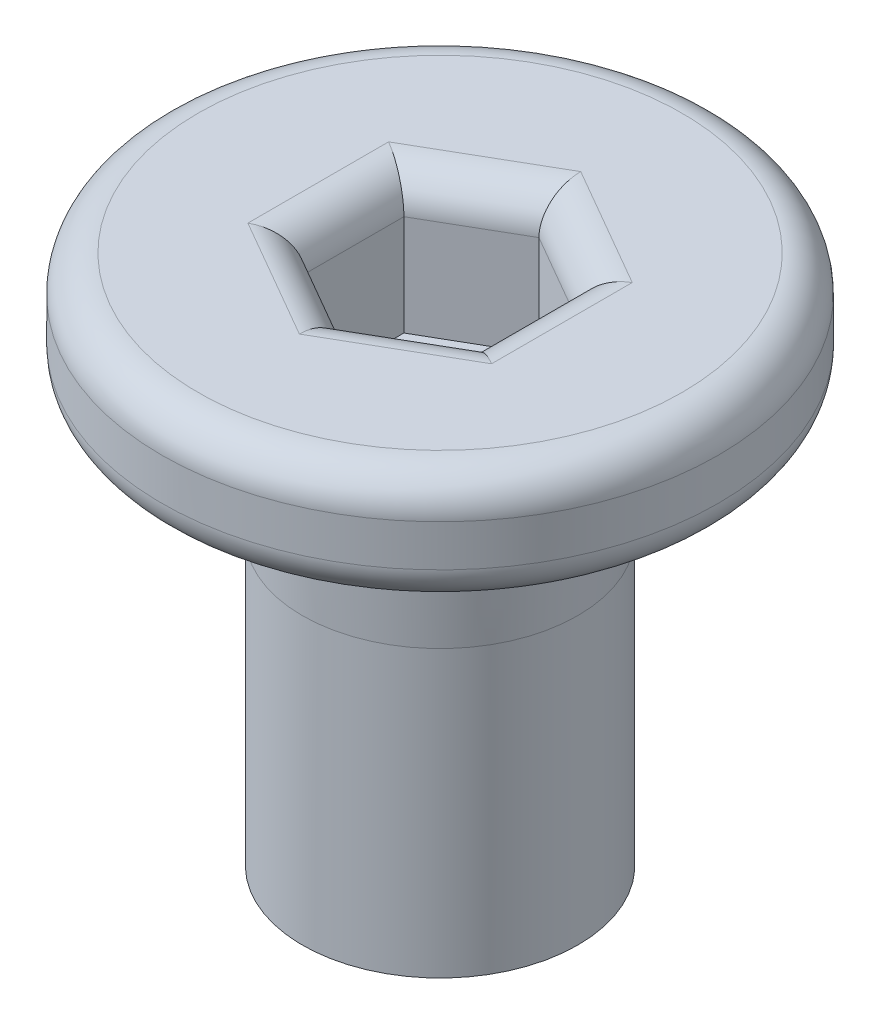
SolidWorks part; units mm, degrees
ref_plane "Front Plane" through (0, 0, 0) normal (0, 0, 1) x (1, 0, 0)
ref_plane "Top Plane" through (0, 0, 0) normal (0, 1, 0) x (1, 0, 0)
ref_plane "Right Plane" through (0, 0, 0) normal (1, 0, 0) x (0, 0, -1)
sketch "Sketch2" plane through (0, 0, 0) normal (0, 0, 1) x (1, 0, 0)
  line L0 (0, -4.65) -> (0, 4.65) construction
  line L1 (0, 4.65) -> (4.875, 4.65)
  line L2 (4.875, 4.65) -> (4.875, 2.65)
  line L3 (4.875, 2.65) -> (2.5, 2.65)
  line L4 (2.5, 2.65) -> (2.413, 0.35)
  line L5 (2.413, 0.35) -> (2.413, -4.65)
  line L6 (2.413, -4.65) -> (0, -4.65)
  line L7 (0, -4.65) -> (0, 4.65)
  point P4 (4.875, 3.65)
  point P5 (0, 0)
  point P11 (2.413, 0.4204)
  point P12 (2.5, 0)
  dimension "D1" = 9.3
  dimension "D2" = 2.413
  dimension "D3" = 4.875
  dimension "D4" = 2
  dimension "D5" = 2.5
  dimension "D6" = 2.3
revolve "Revolve1" add sketch "Sketch2" angle 360 about L0
fillet "Fillet1" radius 0.635 3 edges at (2.5, 2.65, 0) (4.875, 4.65, 0) (4.875, 2.65, 0)
sketch "Sketch3" plane through (0, 4.65, 0) normal (0, 1, 0) x (1, 0, 0)
  line L1 (0, 1.7321) -> (-1.5, 0.866)
  line L2 (-1.5, 0.866) -> (-1.5, -0.866)
  line L3 (-1.5, -0.866) -> (0, -1.7321)
  line L4 (0, -1.7321) -> (1.5, -0.866)
  line L5 (1.5, -0.866) -> (1.5, 0.866)
  line L6 (1.5, 0.866) -> (0, 1.7321)
  circle A0 centre (0, 0) radius 1.5 construction
  dimension "D1" = 3
extrude "Cut-Extrude1" cut sketch "Sketch3" against normal blind 2.4
fillet "Fillet2" radius 0.635 6 edges at (-0.75, 4.65, -1.299) (-1.5, 4.65, 0) (-0.75, 4.65, 1.299) (0.75, 4.65, 1.299) (1.5, 4.65, 0) (0.75, 4.65, -1.299)
